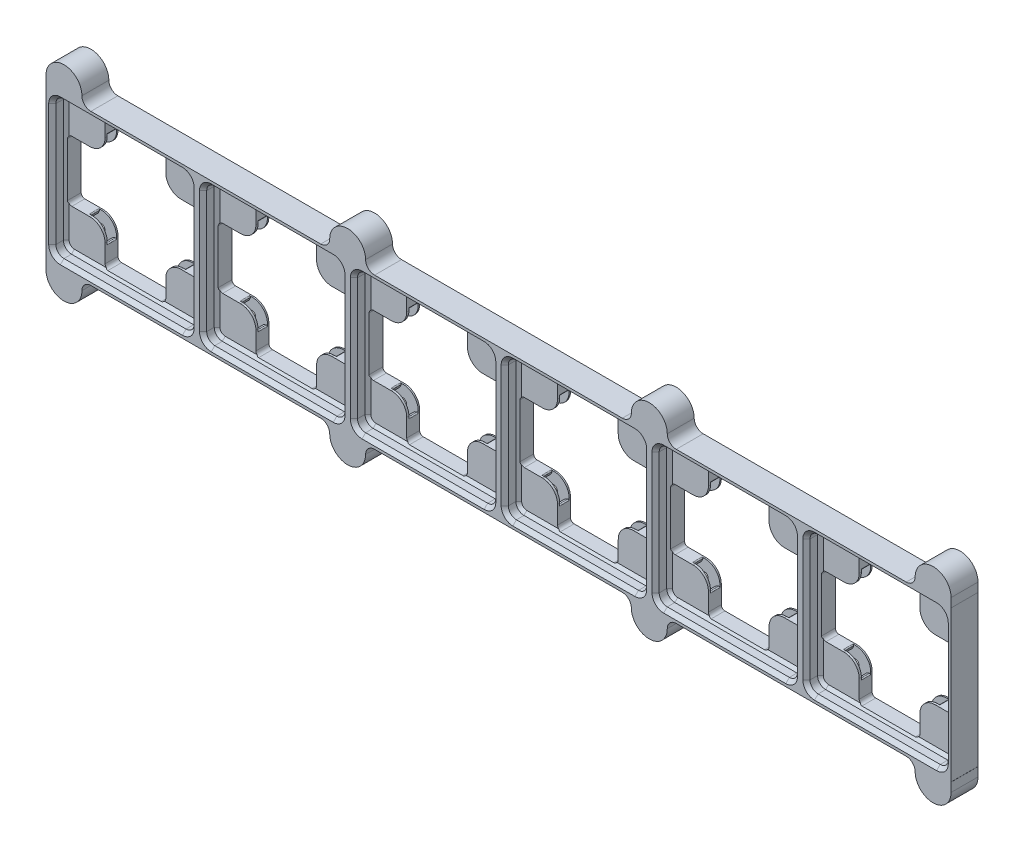
SolidWorks part; units mm, degrees
ref_plane "Front Plane" through (0, 0, 0) normal (0, 0, 1) x (1, 0, 0)
ref_plane "Top Plane" through (0, 0, 0) normal (0, 1, 0) x (1, 0, 0)
ref_plane "Right Plane" through (0, 0, 0) normal (1, 0, 0) x (0, 0, -1)
sketch "Sketch1" plane through (0, 0, 0) normal (0, 0, 1) x (1, 0, 0)
  line L0 (-21, 21) -> (0, 0) construction
  line L1 (-21, 0) -> (-18.7, 0)
  line L2 (-21, 0) -> (-21, 21)
  line L3 (-21, 21) -> (0, 21)
  line L5 (-13.5132, 9.5534) -> (-9.5534, 13.5132) construction
  line L6 (-10.4019, 14.9981) -> (-8.45, 13.0462) construction
  line L7 (-14.9981, 10.4019) -> (-13.0462, 8.45) construction
  line L8 (-13.4235, 8.45) -> (-18.7, 8.45)
  line L9 (-8.45, 13.4235) -> (-8.45, 18.7)
  line L10 (-9.5534, 13.5132) -> (-8.7974, 13.1932)
  line L11 (-13.5132, 9.5534) -> (-13.1932, 8.7974)
  line L12 (0, 18.7) -> (0, 21)
  line L13 (-8.45, 18.7) -> (0, 18.7)
  line L16 (-18.7, 0) -> (-18.7, 8.45)
  line L17 (-18.7, 18.7) -> (-2.3, 18.7) construction
  line L18 (-18.7, 2.3) -> (-18.7, 18.7) construction
  line L19 (-2.3, 2.3) -> (-2.3, 18.7) construction
  line L20 (-18.7, 2.3) -> (-2.3, 2.3) construction
  line L21 (0, 0) -> (0, 21) construction
  line L22 (-21, 0) -> (0, 0) construction
  arc A0 (-9.5534, 13.5132) -> (-13.5132, 9.5534) centre (-12.7, 12.7) ccw
  arc A2 (-13.4235, 8.45) -> (-13.1932, 8.7974) centre (-13.4235, 8.7) ccw
  arc A3 (-8.45, 13.4235) -> (-8.7974, 13.1932) centre (-8.7, 13.4235) cw
  circle A4 centre (-12.7, 12.7) radius 4.25 construction
  point P11 (-11.5333, 11.5333)
  dimension "D3" = 6.5
  dimension "D2" = 0.25
  dimension "D8" = 8.5
  dimension "D1" = 21
  dimension "D4" = 8.3
  dimension "D5" = 8.3
  dimension "D6" = 5.6
  dimension "D7" = 2.3
extrude "Magnet Slot" add sketch "Sketch1" along normal blind 2.6
sketch "Sketch2" plane through (0, 0, 2.6) normal (0, 0, 1) x (1, 0, 0)
  line L0 (-8.7974, 13.1932) -> (-9.5534, 13.5132)
  line L2 (-13.5132, 9.5534) -> (-13.1932, 8.7974)
  line L4 (-13.4235, 8.45) -> (-18.7, 8.45)
  line L5 (-12.7, 8.45) -> (-18.7, 8.45)
  line L6 (-18.7, 8.45) -> (-18.7, 0)
  line L7 (-18.7, 8.45) -> (-18.7, 0)
  line L8 (-18.7, 0) -> (-21, 0)
  line L9 (-18.7, 0) -> (-21, 0)
  line L10 (-21, 0) -> (-21, 21)
  line L11 (-21, 0) -> (-21, 21)
  line L12 (-21, 21) -> (0, 21)
  line L13 (-21, 21) -> (0, 21)
  line L14 (0, 21) -> (0, 18.7)
  line L15 (0, 21) -> (0, 18.7)
  line L16 (0, 18.7) -> (-8.45, 18.7)
  line L17 (0, 18.7) -> (-8.45, 18.7)
  line L18 (-8.45, 18.7) -> (-8.45, 13.4235)
  line L19 (-8.45, 18.7) -> (-8.45, 12.7)
  arc A0 (-9.5534, 13.5132) -> (-13.5132, 9.5534) centre (-12.7, 12.7) ccw
  arc A2 (-13.4235, 8.45) -> (-13.1932, 8.7974) centre (-13.4235, 8.7) ccw
  arc A4 (-8.7974, 13.1932) -> (-8.45, 13.4235) centre (-8.7, 13.4235) ccw
  arc A6 (-12.7, 8.45) -> (-8.45, 12.7) centre (-12.7, 12.7) ccw
  dimension "D1" = 8.5
extrude "Magnet Topper" add sketch "Sketch2" along normal blind 0.6
sketch "Sketch3" plane through (0, 0, 0) normal (0, 0, -1) x (-1, 0, 0)
  line L8 (18.7, 8.45) -> (18.7, 0)
  line L9 (12.7, 8.45) -> (18.7, 8.45)
  line L10 (8.45, 18.7) -> (8.45, 12.7)
  line L11 (0, 18.7) -> (8.45, 18.7)
  line L12 (0, 21) -> (0, 18.7)
  line L13 (21, 21) -> (0, 21)
  line L14 (21, 0) -> (21, 21)
  line L15 (18.7, 0) -> (21, 0)
  line L16 (18.7, 8.45) -> (18.7, 0)
  line L17 (12.7, 8.45) -> (18.7, 8.45)
  line L18 (8.45, 18.7) -> (8.45, 12.7)
  line L19 (0, 18.7) -> (8.45, 18.7)
  line L20 (0, 21) -> (0, 18.7)
  line L21 (21, 21) -> (0, 21)
  line L22 (21, 0) -> (21, 21)
  line L23 (18.7, 0) -> (21, 0)
  arc A1 (8.45, 12.7) -> (12.7, 8.45) centre (12.7, 12.7) ccw
  arc A2 (8.45, 12.7) -> (12.7, 8.45) centre (12.7, 12.7) ccw
  dimension "D1" = 0
extrude "Bottom" add sketch "Sketch3" along normal blind 0.4
sketch "Sketch4" plane through (0, 0, -0.4) normal (0, 0, -1) x (-1, 0, 0)
  line L0 (12.7, 12.7) -> (21, 21) construction
  line L1 (21, 21) -> (0, 21) construction
  line L2 (21, 0) -> (21, 21) construction
  line L3 (12.7, 12.7) -> (16.2355, 16.2355) construction
  line L4 (11.9929, 13.4071) -> (15.5284, 16.9426)
  line L5 (13.4071, 11.9929) -> (16.9426, 15.5284)
  arc A0 (13.5132, 9.5534) -> (9.5534, 13.5132) centre (12.7, 12.7) ccw construction
  arc A1 (13.5132, 9.5534) -> (9.5534, 13.5132) centre (12.7, 12.7) ccw construction
  arc A2 (11.9929, 13.4071) -> (13.4071, 11.9929) centre (12.7, 12.7) ccw
  arc A3 (16.9426, 15.5284) -> (15.5284, 16.9426) centre (16.2355, 16.2355) ccw
  point P3 (14.4678, 14.4678)
  dimension "D1" = 5
extrude "Cut-Extrude1" cut sketch "Sketch4" against normal up to surface (3 mm away) up to face at (-11.3138, 11.3138, 2.6)
fillet "Fillet1" radius 1 2 edges at (-8.45, 18.7, 1.4) (-18.7, 8.45, 1.4)
sketch "Sketch5" plane through (0, 0, 3.2) normal (0, 0, 1) x (1, 0, 0)
  line L0 (0, 21) -> (-17.25, 21)
  line L1 (-21, 17.25) -> (-21, 0)
  line L2 (0, 19.25) -> (-17, 19.25)
  line L3 (-19.25, 17) -> (-19.25, 0)
  line L4 (-21, 0) -> (-19.25, 0)
  line L5 (0, 21) -> (0, 19.25)
  line L6 (0, 19.25) -> (-19.25, 19.25) construction
  line L7 (-19.25, 19.25) -> (-19.25, 0) construction
  line L8 (0, 21) -> (-21, 21) construction
  line L9 (-21, 21) -> (-21, 0) construction
  line L10 (-17.25, 21) -> (-21, 21)
  line L11 (-21, 21) -> (-21, 17.25)
  arc A0 (-17, 19.25) -> (-19.25, 17) centre (-17, 17) ccw
  point P15 (-21, 21)
  dimension "D2" = 2.25
  dimension "D1" = 1.75
extrude "Boss-Extrude1" add sketch "Sketch5" along normal blind 3.9
chamfer "Chamfer1" distance 0.8 angle 45 3 edges at (-19.25, 8.5, 3.2) (-18.591, 18.591, 3.2) (-8.5, 19.25, 3.2)
chamfer "Chamfer2" distance 1 angle 45 3 edges at (-8.5, 19.25, 7.1) (-18.591, 18.591, 7.1) (-19.25, 8.5, 7.1)
ref_axis "Center Axis" through (0, 0, 0) along (0, 0, 1)
pattern_circular "CirPattern1" count 4 over 360 about axis through (0, 0, 0) along (0, 0, 1) of bodies 105
combine bodies "Combine1" bodies to combine 105 108 106 107
pattern_linear "LPattern2" count 6 spacing 42 along (1, 0, 0) of bodies 156
combine bodies "Combine2" operation type add bodies to combine 156 162 161 160 159 158
sketch "Sketch27" plane through (0, 0, 7.1) normal (0, 0, 1) x (1, 0, 0)
  line L0 (-21, -21) -> (231, -21) construction
  line L1 (-21, -21) -> (231, -21) construction
  line L2 (-21, -23.5) -> (231, -23.5) construction
  line L3 (-21, 21) -> (-21, -21) construction
  line L4 (-21, 21) -> (-21, -21) construction
  line L5 (-16, -21) -> (-16, -36.8408) construction
  line L6 (-21, -21) -> (-21, -23.5)
  line L7 (-11, -23.5) -> (-11, -21)
  line L8 (-11, -21) -> (-21, -21)
  line L9 (59, -20.25) -> (67, -20.25) construction
  line L10 (63, -20.25) -> (63, -21) construction
  line L11 (143, -20.25) -> (151, -20.25) construction
  line L12 (147, -20.25) -> (146.9714, -21) construction
  line L13 (231, -21) -> (231, 21) construction
  line L14 (231, -21) -> (231, 21) construction
  line L15 (226, -21) -> (226, 21) construction
  line L16 (68, -23.5) -> (68, -21)
  line L17 (68, -21) -> (58, -21)
  line L18 (58, -21) -> (58, -23.5)
  line L19 (142, -21) -> (142, -23.5)
  line L20 (63, -23.5) -> (315, -23.5) construction
  line L21 (147, -20.25) -> (147, -21) construction
  line L22 (143, -20.25) -> (151, -20.25) construction
  line L23 (152, -23.5) -> (152, -21)
  line L24 (63, -21) -> (315, -21) construction
  line L25 (152, -21) -> (142, -21)
  line L26 (221.0286, -21) -> (221.0286, -23.5)
  line L27 (142.0286, -23.5) -> (394.0286, -23.5) construction
  line L28 (231.0286, -21) -> (221.0286, -21)
  line L29 (222.0286, -20.25) -> (230.0286, -20.25) construction
  line L30 (142.0286, -21) -> (394.0286, -21) construction
  line L31 (58.0286, -23.5) -> (310.0286, -23.5) construction
  line L32 (222.0286, -20.25) -> (230.0286, -20.25) construction
  line L33 (231.0286, -23.5) -> (231.0286, -21)
  line L34 (58.0286, -21) -> (310.0286, -21) construction
  line L35 (226.0286, -20.25) -> (226, -21) construction
  line L36 (226.0286, -20.25) -> (226.0286, -21) construction
  arc A0 (-21, -23.5) -> (-11, -23.5) centre (-16, -23.5) ccw
  arc A1 (58, -23.5) -> (68, -23.5) centre (63, -23.5) ccw
  arc A2 (142, -23.5) -> (152, -23.5) centre (147, -23.5) ccw
  arc A3 (221.0286, -23.5) -> (231.0286, -23.5) centre (226.0286, -23.5) ccw
  dimension "D3" = 10
  dimension "D2" = 5
  dimension "D4" = 5
  dimension "D1" = 2.5
extrude "Boss-Extrude6" add sketch "Sketch27" against normal up to surface (7.5 mm away) up to face at (0, 0, -0.4)
sketch "Sketch28" plane through (0, 0, -0.4) normal (0, 0, -1) x (-1, 0, 0)
  circle A0 centre (-226.0286, -23.5) radius 2.5
  circle A1 centre (-147, -23.5) radius 2.5
  circle A2 centre (-63, -23.5) radius 2.5
  circle A3 centre (16, -23.5) radius 2.5
  dimension "D1" = 5
  dimension "D2" = 5
  dimension "D3" = 5
  dimension "D4" = 5
extrude "Cut-Extrude6" cut sketch "Sketch28" against normal blind 6.5
ref_plane "Plane3" through (0, 0, 0) normal (0, -1, 0) x (-1, 0, 0)
mirror "Mirror7" about plane through (0, 0, 0) normal (0, -1, 0) of "Cut-Extrude6", "Boss-Extrude6"
fillet "Fillet12" radius 2.5 12 edges at (221.0286, -21, 3.35) (152, -21, 3.35) (142, -21, 3.35) (68, -21, 3.35) (58, -21, 3.35) (-11, -21, 3.35) (-11, 21, 3.35) (68, 21, 3.35) (58, 21, 3.35) (142, 21, 3.35) (152, 21, 3.35) (221.0286, 21, 3.35)
